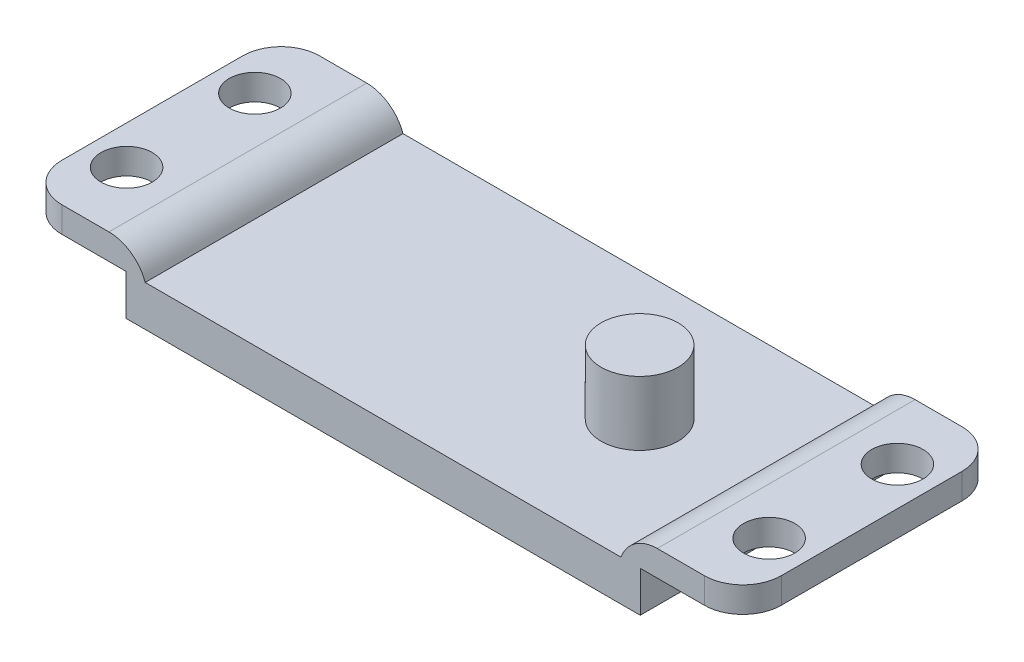
SolidWorks part; units mm, degrees
ref_plane "Front Plane" through (0, 0, 0) normal (0, 0, 1) x (1, 0, 0)
ref_plane "Top Plane" through (0, 0, 0) normal (0, 1, 0) x (1, 0, 0)
ref_plane "Right Plane" through (0, 0, 0) normal (1, 0, 0) x (0, 0, -1)
sketch "Sketch1" plane through (0, 0, 0) normal (0, 1, 0) x (1, 0, 0)
  line L1 (-20.05, -10.05) -> (20.05, -10.05)
  line L2 (-20.05, -10.05) -> (-20.05, 10.05)
  line L3 (-20.05, 10.05) -> (20.05, 10.05)
  line L4 (20.05, -10.05) -> (20.05, 10.05)
  line L5 (-20.05, -10.05) -> (20.05, 10.05) construction
  line L6 (-20.05, 10.05) -> (20.05, -10.05) construction
  point P0 (0, 0)
  dimension "D1" = 40.1
  dimension "D2" = 20.1
extrude "Boss-Extrude1" add sketch "Sketch1" along normal blind 3.175
sketch "Sketch2" plane through (0, 3.175, 0) normal (0, 1, 0) x (1, 0, 0)
  line L0 (-20.05, -10.05) -> (20.05, -10.05) construction
  line L1 (20.05, 10.05) -> (18.55, 10.05)
  line L2 (20.05, 10.05) -> (20.05, -10.05)
  line L3 (20.05, -10.05) -> (18.55, -10.05)
  line L4 (18.55, 10.05) -> (18.55, -10.05)
  dimension "D1" = 1.5
extrude "Boss-Extrude2" add sketch "Sketch2" along normal blind 2
sketch "Sketch3" plane through (20.05, 0, 0) normal (1, 0, 0) x (0, 0, -1)
  line L0 (10.05, 5.175) -> (10.05, 0) construction
  line L1 (-10.05, 5.175) -> (10.05, 5.175)
  line L2 (-10.05, 5.175) -> (-10.05, 3.175)
  line L3 (-10.05, 3.175) -> (10.05, 3.175)
  line L4 (10.05, 5.175) -> (10.05, 3.175)
  line L5 (10.05, 5.175) -> (10.05, 3.175) construction
extrude "Boss-Extrude3" add sketch "Sketch3" along normal blind 8
sketch "Sketch4" plane through (0, 3.175, 0) normal (0, -1, 0) x (1, 0, 0)
  line L0 (25.05, 5) -> (25.05, -5) construction
  line L1 (1.7463, 0) -> (-1.7463, 0) construction
  line L2 (20.05, 10.05) -> (20.05, -10.05) construction
  circle A0 centre (25.05, 5) radius 2
  circle A1 centre (25.05, -5) radius 2
  point P4 (25.05, 0)
  point P5 (0, 0)
  dimension "D1" = 4
  dimension "D2" = 10
  dimension "D3" = 5
extrude "Cut-Extrude1" cut sketch "Sketch4" against normal through all both and the other way through all
fillet "Fillet1" radius 3 1 edges at (18.55, 5.175, 0)
fillet "Fillet2" radius 3 2 edges at (28.05, 4.175, -10.05) (28.05, 4.175, 10.05)
mirror "Mirror2" about plane through (0, 0, 0) normal (1, 0, 0) of "Fillet2", "Fillet1", "Cut-Extrude1", "Boss-Extrude3", "Boss-Extrude2"
sketch "Sketch5" plane through (0, 3.175, 0) normal (0, 1, 0) x (1, 0, 0)
  circle A0 centre (9.95, 0) radius 3
  circle A1 centre (25.05, -5) radius 2 construction
  point P2 (0, 0)
  dimension "D1" = 6
  dimension "D2" = 15.1
extrude "Boss-Extrude4" add sketch "Sketch5" along normal blind 5
